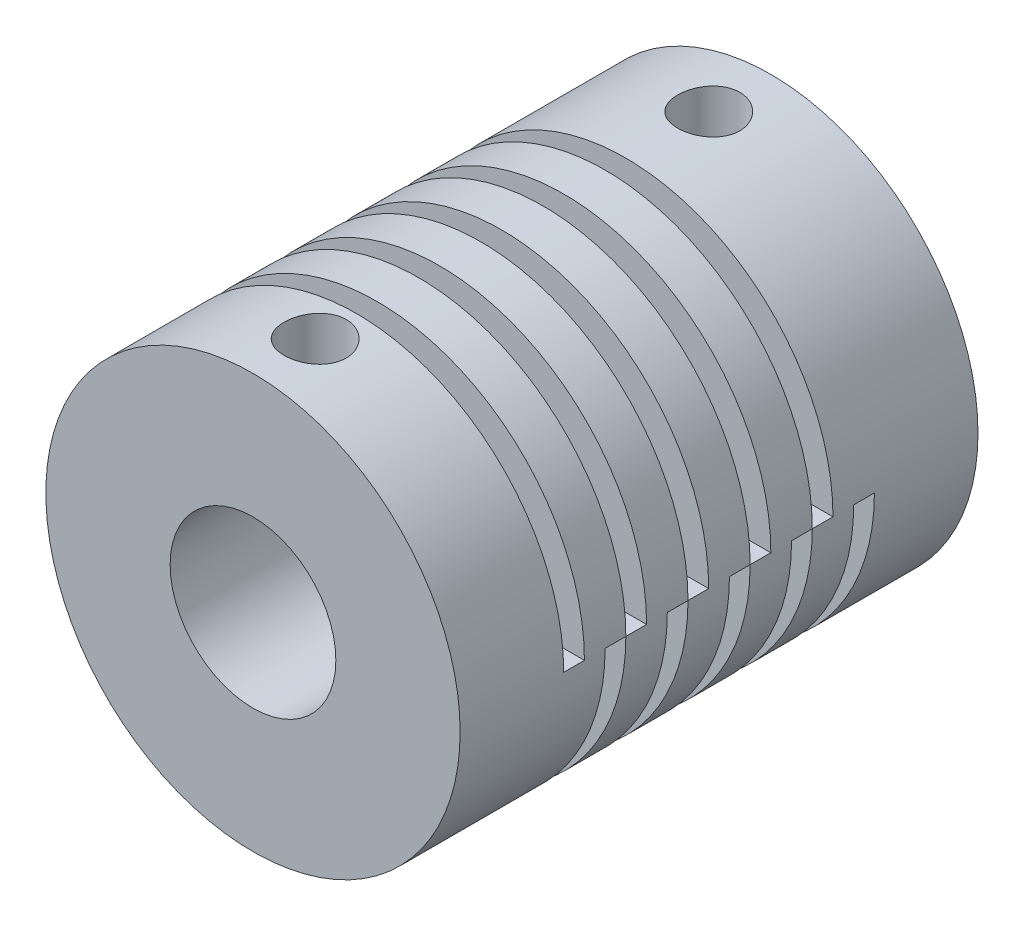
SolidWorks part; units mm, degrees
ref_plane "Front Plane" through (0, 0, 0) normal (0, 0, 1) x (1, 0, 0)
ref_plane "Top Plane" through (0, 0, 0) normal (0, 1, 0) x (1, 0, 0)
ref_plane "Right Plane" through (0, 0, 0) normal (1, 0, 0) x (0, 0, -1)
sketch "Sketch1" plane through (0, 0, 0) normal (0, 0, 1) x (1, 0, 0)
  circle A0 centre (0, 0) radius 10
  circle A1 centre (0, 0) radius 4
  dimension "D1" = 20
  dimension "D2" = 8
extrude "Boss-Extrude1" add sketch "Sketch1" along normal blind 25
sketch "Sketch2" plane through (0, 0, 0) normal (1, 0, 0) x (0, 0, -1)
  line L0 (0, 10) -> (-25, 10) construction
  line L1 (-20, 10) -> (-19, 10)
  line L2 (-20, 10) -> (-20, 0)
  line L3 (-20, 0) -> (-19, 0)
  line L4 (-19, 10) -> (-19, 0)
  line L5 (-25, -10) -> (0, -10) construction
  line L6 (-18, -10) -> (-17, -10)
  line L7 (-18, -10) -> (-18, 0)
  line L8 (-18, 0) -> (-17, 0)
  line L9 (-17, -10) -> (-17, 0)
  line L10 (-25, 10) -> (-25, -10) construction
  dimension "D1" = 1
  dimension "D2" = 1
  dimension "D3" = 1
  dimension "D4" = 10
  dimension "D5" = 10
  dimension "D6" = 5
extrude "Cut-Extrude1" cut sketch "Sketch2" against normal blind 25 and the other way blind 25
pattern_linear "LPattern1" count 5 spacing 3 along (0, 0, -1) of "Cut-Extrude1"
sketch "Sketch3" plane through (0, 0, 0) normal (0, 1, 0) x (1, 0, 0)
  line L0 (-10, -25) -> (10, -25) construction
  circle A0 centre (0, -3) radius 1.5
  circle A1 centre (0, -22) radius 1.5
  point P7 (0, 0)
  dimension "D1" = 3
  dimension "D2" = 3
  dimension "D3" = 3
  dimension "D4" = 3
extrude "Cut-Extrude2" cut sketch "Sketch3" against normal blind 10 from offset 10
